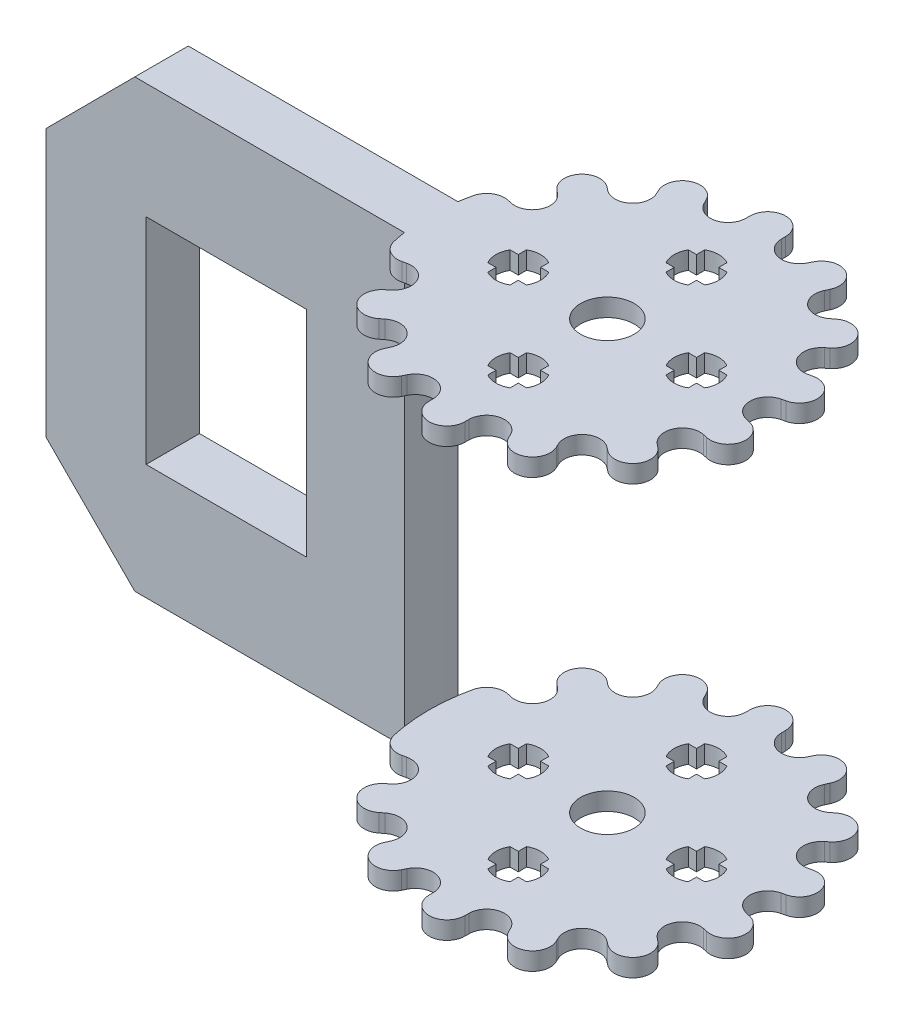
SolidWorks part; units mm, degrees
note: '?' marks a value the reader was unsure of. The reader was unsure of these and kept them because the rebuilt part matched: shared geometry of "Croquis1<3>".
material "PLA"
ref_plane "Alzado" through (0, 0, 0) normal (0, 0, 1) x (1, 0, 0)
ref_plane "Planta" through (0, 0, 0) normal (0, 1, 0) x (1, 0, 0)
ref_plane "Vista lateral" through (0, 0, 0) normal (1, 0, 0) x (0, 0, -1)
sketch "Croquis1" plane through (0, 0, 0) normal (0, 1, 0) x (1, 0, 0)
  line L4 (-60, -20) -> (-60, -14)
  line L5 (-60, -20) -> (0, -20)
  line L6 (0, 0) -> (-60, 0) construction
  line L7 (-60, 0) -> (-60, 3) construction
  line L8 (-60, 3) -> (-60, -14)
  line L9 (-60, 3) -> (-19.7737, 3)
  circle A0 centre (0, 0) radius 20 construction
  arc A1 (-14.2829, -14) -> (0, -20) centre (0, 0) ccw
  arc A2 (-14.1107, -14.1735) -> (0, -20) centre (0, 0) cw
extrude "Saliente-Extruir1" add sketch "Croquis1" along normal blind 50
extrude "Saliente-Extruir2" add sketch "Croquis1<3>" along normal blind 2 contours A2 A1
sketch "Croquis1<3>" plane through (0, 0, 0) normal (0, 1, 0) x (1, 0, 0) same geometry as "Croquis1"
ref_plane "Plano1" through (0, 25, 0) normal (0, 1, 0) x (1, 0, 0)
mirror "Simetría1" about plane through (0, 25, 0) normal (0, 1, 0) of "Saliente-Extruir2"
sketch "Croquis2" plane through (0, 50, 0) normal (0, 1, 0) x (1, 0, 0)
  line L0 (2, 18) -> (2.0054, 17.5487)
  line L1 (0, 20) -> (0, 16) construction
  line L2 (9.6118, 15.3497) -> (9.4209, 14.9407)
  line L3 (15.3199, 9.6592) -> (14.9705, 9.3736)
  line L4 (17.9937, 2.0555) -> (17.555, 1.9499)
  line L5 (17.1037, -5.9552) -> (16.6625, -5.8601)
  line L6 (12.826, -12.7865) -> (12.4698, -12.5093)
  line L7 (6.008, -17.0852) -> (5.8073, -16.6809)
  line L8 (-2, -18) -> (-2.0054, -17.5487)
  line L9 (-9.6118, -15.3497) -> (-9.4209, -14.9407)
  line L10 (-15.3199, -9.6592) -> (-14.9705, -9.3736)
  line L11 (-17.9937, -2.0555) -> (-17.555, -1.9499)
  line L12 (-17.1037, 5.9552) -> (-16.6625, 5.8601)
  line L13 (-12.826, 12.7865) -> (-12.4698, 12.5093)
  line L14 (-6.008, 17.0852) -> (-5.8073, 16.6809)
  line L15 (-2, 18) -> (-2.0054, 17.5487)
  line L16 (6.008, 17.0852) -> (5.8073, 16.6809)
  line L17 (12.826, 12.7865) -> (12.4698, 12.5093)
  line L18 (17.1037, 5.9552) -> (16.6625, 5.8601)
  line L19 (17.9937, -2.0555) -> (17.555, -1.9499)
  line L20 (15.3199, -9.6592) -> (14.9705, -9.3736)
  line L21 (9.6118, -15.3497) -> (9.4209, -14.9407)
  line L22 (2, -18) -> (2.0054, -17.5487)
  line L23 (-6.008, -17.0852) -> (-5.8073, -16.6809)
  line L24 (-12.826, -12.7865) -> (-12.4698, -12.5093)
  line L25 (-17.1037, -5.9552) -> (-16.6625, -5.8601)
  line L26 (-17.9937, 2.0555) -> (-17.555, 1.9499)
  line L27 (-15.3199, 9.6592) -> (-14.9705, 9.3736)
  line L28 (-9.6118, 15.3497) -> (-9.4209, 14.9407)
  circle A0 centre (0, 0) radius 20 construction
  circle A1 centre (0, 0) radius 16 construction
  circle A2 centre (0, 18) radius 2 construction
  circle A3 centre (4.0054, 17.5487) radius 2 construction
  circle A4 centre (7.8099, 16.2174) radius 2 construction
  circle A5 centre (11.2228, 14.073) radius 2 construction
  circle A6 centre (14.073, 11.2228) radius 2 construction
  circle A7 centre (16.2174, 7.8099) radius 2 construction
  circle A8 centre (17.5487, 4.0054) radius 2 construction
  circle A9 centre (18, 0) radius 2 construction
  circle A10 centre (17.5487, -4.0054) radius 2 construction
  circle A11 centre (16.2174, -7.8099) radius 2 construction
  circle A12 centre (14.073, -11.2228) radius 2 construction
  circle A13 centre (11.2228, -14.073) radius 2 construction
  circle A14 centre (7.8099, -16.2174) radius 2 construction
  circle A15 centre (4.0054, -17.5487) radius 2 construction
  circle A16 centre (0, -18) radius 2 construction
  circle A17 centre (-4.0054, -17.5487) radius 2 construction
  circle A18 centre (-7.8099, -16.2174) radius 2 construction
  circle A19 centre (-11.2228, -14.073) radius 2 construction
  circle A20 centre (-14.073, -11.2228) radius 2 construction
  circle A21 centre (-16.2174, -7.8099) radius 2 construction
  circle A22 centre (-17.5487, -4.0054) radius 2 construction
  circle A23 centre (-18, 0) radius 2 construction
  circle A24 centre (-17.5487, 4.0054) radius 2 construction
  circle A25 centre (-16.2174, 7.8099) radius 2 construction
  circle A26 centre (-14.073, 11.2228) radius 2 construction
  circle A27 centre (-11.2228, 14.073) radius 2 construction
  circle A28 centre (-7.8099, 16.2174) radius 2 construction
  circle A29 centre (-4.0054, 17.5487) radius 2 construction
  arc A30 (-2, 18) -> (2, 18) centre (0, 18) cw
  arc A31 (2.0054, 17.5487) -> (4.0054, 15.5487) centre (4.0054, 17.5487) ccw
  arc A32 (6.008, 17.0852) -> (9.6118, 15.3497) centre (7.8099, 16.2174) cw
  arc A33 (9.4209, 14.9407) -> (10.355, 12.271) centre (11.2228, 14.073) ccw
  arc A34 (12.826, 12.7865) -> (15.3199, 9.6592) centre (14.073, 11.2228) cw
  arc A35 (14.9705, 9.3736) -> (14.6538, 6.5629) centre (16.2174, 7.8099) ccw
  arc A36 (17.1037, 5.9552) -> (17.9937, 2.0555) centre (17.5487, 4.0054) cw
  arc A37 (17.555, 1.9499) -> (16.0501, -0.445) centre (18, 0) ccw
  arc A38 (17.9937, -2.0555) -> (17.1037, -5.9552) centre (17.5487, -4.0054) cw
  arc A39 (16.6625, -5.8601) -> (14.2676, -7.3649) centre (16.2174, -7.8099) ccw
  arc A40 (15.3199, -9.6592) -> (12.826, -12.7865) centre (14.073, -11.2228) cw
  arc A41 (12.4698, -12.5093) -> (9.6592, -12.826) centre (11.2228, -14.073) ccw
  arc A42 (9.6118, -15.3497) -> (6.008, -17.0852) centre (7.8099, -16.2174) cw
  arc A43 (5.8073, -16.6809) -> (3.1376, -15.7468) centre (4.0054, -17.5487) ccw
  arc A44 (2, -18) -> (-2, -18) centre (0, -18) cw
  arc A45 (-2.0054, -17.5487) -> (-4.0054, -15.5487) centre (-4.0054, -17.5487) ccw
  arc A46 (-6.008, -17.0852) -> (-9.6118, -15.3497) centre (-7.8099, -16.2174) cw
  arc A47 (-9.4209, -14.9407) -> (-10.355, -12.271) centre (-11.2228, -14.073) ccw
  arc A48 (-12.826, -12.7865) -> (-15.3199, -9.6592) centre (-14.073, -11.2228) cw
  arc A49 (-14.9705, -9.3736) -> (-14.6538, -6.5629) centre (-16.2174, -7.8099) ccw
  arc A50 (-17.1037, -5.9552) -> (-17.9937, -2.0555) centre (-17.5487, -4.0054) cw
  arc A51 (-17.555, -1.9499) -> (-16.0501, 0.445) centre (-18, 0) ccw
  arc A52 (-17.9937, 2.0555) -> (-17.1037, 5.9552) centre (-17.5487, 4.0054) cw
  arc A53 (-16.6625, 5.8601) -> (-14.2676, 7.3649) centre (-16.2174, 7.8099) ccw
  arc A54 (-15.3199, 9.6592) -> (-12.826, 12.7865) centre (-14.073, 11.2228) cw
  arc A55 (-12.4698, 12.5093) -> (-9.6592, 12.826) centre (-11.2228, 14.073) ccw
  arc A56 (-9.6118, 15.3497) -> (-6.008, 17.0852) centre (-7.8099, 16.2174) cw
  arc A57 (-5.8073, 16.6809) -> (-3.1376, 15.7468) centre (-4.0054, 17.5487) ccw
  arc A58 (-2.0054, 17.5487) -> (-3.1376, 15.7468) centre (-4.0054, 17.5487) cw
  arc A59 (5.8073, 16.6809) -> (4.0054, 15.5487) centre (4.0054, 17.5487) cw
  arc A60 (12.4698, 12.5093) -> (10.355, 12.271) centre (11.2228, 14.073) cw
  arc A61 (16.6625, 5.8601) -> (14.6538, 6.5629) centre (16.2174, 7.8099) cw
  arc A62 (17.555, -1.9499) -> (16.0501, -0.445) centre (18, 0) cw
  arc A63 (14.9705, -9.3736) -> (14.2676, -7.3649) centre (16.2174, -7.8099) cw
  arc A64 (9.4209, -14.9407) -> (9.6592, -12.826) centre (11.2228, -14.073) cw
  arc A65 (2.0054, -17.5487) -> (3.1376, -15.7468) centre (4.0054, -17.5487) cw
  arc A66 (-5.8073, -16.6809) -> (-4.0054, -15.5487) centre (-4.0054, -17.5487) cw
  arc A67 (-12.4698, -12.5093) -> (-10.355, -12.271) centre (-11.2228, -14.073) cw
  arc A68 (-16.6625, -5.8601) -> (-14.6538, -6.5629) centre (-16.2174, -7.8099) cw
  arc A69 (-17.555, 1.9499) -> (-16.0501, 0.445) centre (-18, 0) cw
  arc A70 (-14.9705, 9.3736) -> (-14.2676, 7.3649) centre (-16.2174, 7.8099) cw
  arc A71 (-9.4209, 14.9407) -> (-9.6592, 12.826) centre (-11.2228, 14.073) cw
  point P65 (0, 0)
  point P150 (0, 0)
  point P206 (0, 0)
  dimension "D1" = 28
  dimension "D2" = 14
  dimension "D3" = 14
extrude "Cortar-Extruir2" cut sketch "Croquis2" against normal blind 2 contours A62 L19 A38 A2 A36 L4 A37 | A61 L18 A36 A2 A34 L3 A35 | A70 L27 A54 A2 A52 L12 A53 | A71 L28 A56 A2 A54 L13 A55 | A58 L15 A30 A2 A56 L14 A57 | A59 L16 A32 A2 A30 L0 A31 | A60 L17 A34 A2 A32 L2 A33 | A63 L20 A40 A2 A38 L5 A39 | A64 L21 A42 A2 A40 L6 A41 | A65 L22 A44 A2 A42 L7 A43
mirror "Simetría2" about plane through (0, 25, 0) normal (0, 1, 0) of "Cortar-Extruir2"
sketch "Croquis3" plane through (0, 50, 0) normal (0, 1, 0) x (1, 0, 0)
  circle A0 centre (0, 0) radius 3
  point P4 (0, 0)
extrude "Cortar-Extruir3" cut sketch "Croquis3" against normal up to next
mirror "Simetría3" about plane through (0, 25, 0) normal (0, 1, 0) of "Cortar-Extruir3"
ref_plane "Plano2" through (0, 25, 0) normal (0, -1, 0) x (-1, 0, 0)
sketch "Croquis5" plane through (0, 25, 0) normal (0, -1, 0) x (-1, 0, 0)
  line L1 (-22.6575, 23.4045) -> (62.2625, 23.4045)
  line L2 (-22.6575, 23.4045) -> (-22.6575, -22.6962)
  line L3 (-22.6575, -22.6962) -> (62.2625, -22.6962)
  line L4 (62.2625, 23.4045) -> (62.2625, -22.6962)
  line L5 (-22.6575, 23.4045) -> (62.2625, -22.6962) construction
  line L6 (-22.6575, -22.6962) -> (62.2625, 23.4045) construction
  point P0 (19.8025, 0.3542)
ref_axis "Eje1" through (0, 0, 0) along (0, 1, 0)?
sketch "Croquis8" plane through (0, 50, 0) normal (0, 1, 0) x (1, 0, 0)
  line L0 (0, 0) -> (-60, 0) construction
  line L1 (-60, 0) -> (-60, -3) construction
  line L2 (-60, 3) -> (-60, -14) construction
  line L3 (-60, -3) -> (-19.7737, -3)
  line L4 (-60, -3) -> (-60, -20)
  line L5 (-60, -20) -> (0, -20)
  arc A0 (0, -20) -> (-14.1107, -14.1735) centre (0, 0) ccw construction
  arc A1 (-19.7737, -3) -> (0, -20) centre (0, 0) ccw
extrude "Cortar-Extruir6" cut sketch "Croquis8" against normal through all
sketch "Croquis9" plane through (0, 50, 0) normal (0, 1, 0) x (1, 0, 0)
  line L0 (-2.0054, -17.5487) -> (-2, -18)
  line L1 (-5.8073, -16.6809) -> (-6.008, -17.0852)
  line L2 (-9.4209, -14.9407) -> (-9.6118, -15.3497)
  line L3 (-12.4698, -12.5093) -> (-12.826, -12.7865)
  line L4 (-15.3199, -9.6592) -> (-14.9705, -9.3736)
  line L5 (-16.6625, -5.8601) -> (-17.1037, -5.9552)
  arc A0 (-19.4986, -4.4504) -> (-17.1037, -5.9552) centre (-17.5487, -4.0054) ccw
  arc A1 (-17.9937, -2.0555) -> (-17.1037, -5.9552) centre (-17.5487, -4.0054) ccw construction
  arc A2 (-16.6625, -5.8601) -> (-14.9705, -9.3736) centre (-16.2174, -7.8099) cw
  arc A3 (-15.3199, -9.6592) -> (-12.826, -12.7865) centre (-14.073, -11.2228) ccw
  arc A4 (-12.4698, -12.5093) -> (-9.4209, -14.9407) centre (-11.2228, -14.073) cw
  arc A5 (-9.6118, -15.3497) -> (-6.008, -17.0852) centre (-7.8099, -16.2174) ccw
  arc A6 (-5.8073, -16.6809) -> (-2.0054, -17.5487) centre (-4.0054, -17.5487) cw
  arc A7 (-2, -18) -> (0, -20) centre (0, -18) ccw
  circle A8 centre (0, 0) radius 20
  arc M2 (-19.7737, -3) -> (0, -20) centre (0, 0) ccw
extrude "Cortar-Extruir7" cut sketch "Croquis9" against normal through all contours A3 L4 A2 L5 A0 M2 | A5 L2 A4 L3 A3 M2 | A7 L0 A6 L1 A5 M2
sketch "Croquis10" plane through (0, 0, 3) normal (0, 0, 1) x (1, 0, 0)
  line L0 (-19.7737, 25) -> (-59.7459, 25) construction
  line L1 (-19.7737, 2) -> (-19.7737, 48) construction
  line L2 (-22, 25) -> (22, 25) construction
  line L3 (-39.7598, 25) -> (-39.7598, 37.0385) construction
  line L4 (-48.7712, 37.0385) -> (-30.7484, 37.0385)
  line L5 (-30.7484, 37.0385) -> (-30.7484, 12.9615)
  line L6 (-48.7712, 37.0385) -> (-48.7712, 12.9615)
  line L7 (-48.7712, 12.9615) -> (-30.7484, 12.9615)
  line L8 (-60, 50) -> (-60, 40)
  line L9 (-60, 0) -> (-60, 50) construction
  line L10 (-60, 50) -> (-50.0325, 50)
  line L11 (-19.7737, 50) -> (-60, 50) construction
  line L12 (-50.0325, 50) -> (-60, 40)
  line L13 (-60, 0) -> (-60, 10)
  line L14 (-50.0325, 0) -> (-60, 10)
  point P13 (-30.7484, 25)
  point P14 (-48.7712, 25)
  line M8 (-19.7737, 50) -> (-60, 50)
  line M9 (-60, 50) -> (-60, 0)
  line M10 (-60, 0) -> (-19.7737, 0)
extrude "Cortar-Extruir8" cut sketch "Croquis10" against normal blind 10 contours L12 M8 M9 | L6 L7 L5 L4 | L14 M10 M9
sketch "Croquis15" plane through (0, 50, 0) normal (0, 1, 0) x (1, 0, 0)
  line L0 (0, 10) -> (2.5, 10) construction
  line L1 (1.25, 10) -> (1.25, 12.1651) construction
  line L2 (0, 10) -> (0, 12.5) construction
  line L3 (0, 12.5) -> (0, 11.25) construction
  line L4 (0, 11.25) -> (2.1651, 11.25) construction
  line L5 (1.25, 12.1651) -> (1.25, 11.25)
  line L6 (1.25, 11.25) -> (2.1651, 11.25)
  line L7 (2.1651, 8.75) -> (1.25, 8.75)
  line L8 (1.25, 8.75) -> (1.25, 7.8349)
  line L9 (-1.25, 7.8349) -> (-1.25, 8.75)
  line L10 (-1.25, 8.75) -> (-2.1651, 8.75)
  line L11 (-2.1651, 11.25) -> (-1.25, 11.25)
  line L12 (-1.25, 11.25) -> (-1.25, 12.1651)
  line L13 (11.25, -1.25) -> (11.25, -2.1651)
  line L14 (12.1651, -1.25) -> (11.25, -1.25)
  line L15 (8.75, -2.1651) -> (8.75, -1.25)
  line L16 (8.75, -1.25) -> (7.8349, -1.25)
  line L17 (7.8349, 1.25) -> (8.75, 1.25)
  line L18 (8.75, 1.25) -> (8.75, 2.1651)
  line L19 (11.25, 2.1651) -> (11.25, 1.25)
  line L20 (11.25, 1.25) -> (12.1651, 1.25)
  line L21 (-1.25, -11.25) -> (-2.1651, -11.25)
  line L22 (-1.25, -12.1651) -> (-1.25, -11.25)
  line L23 (-2.1651, -8.75) -> (-1.25, -8.75)
  line L24 (-1.25, -8.75) -> (-1.25, -7.8349)
  line L25 (1.25, -7.8349) -> (1.25, -8.75)
  line L26 (1.25, -8.75) -> (2.1651, -8.75)
  line L27 (2.1651, -11.25) -> (1.25, -11.25)
  line L28 (1.25, -11.25) -> (1.25, -12.1651)
  line L29 (-11.25, 1.25) -> (-11.25, 2.1651)
  line L30 (-12.1651, 1.25) -> (-11.25, 1.25)
  line L31 (-8.75, 2.1651) -> (-8.75, 1.25)
  line L32 (-8.75, 1.25) -> (-7.8349, 1.25)
  line L33 (-7.8349, -1.25) -> (-8.75, -1.25)
  line L34 (-8.75, -1.25) -> (-8.75, -2.1651)
  line L35 (-11.25, -2.1651) -> (-11.25, -1.25)
  line L36 (-11.25, -1.25) -> (-12.1651, -1.25)
  circle A0 centre (0, 0) radius 10 construction
  circle A1 centre (0, 10) radius 2.5 construction
  arc A2 (0, 12.5) -> (1.25, 12.1651) centre (0, 10) cw
  arc A3 (2.1651, 11.25) -> (2.5, 10) centre (0, 10) cw
  arc A4 (2.5, 10) -> (2.1651, 8.75) centre (0, 10) cw
  arc A5 (1.25, 7.8349) -> (0, 7.5) centre (0, 10) cw
  arc A6 (0, 7.5) -> (-1.25, 7.8349) centre (0, 10) cw
  arc A7 (-2.1651, 8.75) -> (-2.5, 10) centre (0, 10) cw
  arc A8 (-2.5, 10) -> (-2.1651, 11.25) centre (0, 10) cw
  arc A9 (-1.25, 12.1651) -> (0, 12.5) centre (0, 10) cw
  arc A10 (12.1651, 1.25) -> (12.5, 0) centre (10, 0) cw
  arc A11 (12.5, 0) -> (12.1651, -1.25) centre (10, 0) cw
  arc A12 (11.25, -2.1651) -> (10, -2.5) centre (10, 0) cw
  arc A13 (10, -2.5) -> (8.75, -2.1651) centre (10, 0) cw
  arc A14 (7.8349, -1.25) -> (7.5, 0) centre (10, 0) cw
  arc A15 (7.5, 0) -> (7.8349, 1.25) centre (10, 0) cw
  arc A16 (8.75, 2.1651) -> (10, 2.5) centre (10, 0) cw
  arc A17 (10, 2.5) -> (11.25, 2.1651) centre (10, 0) cw
  arc A18 (1.25, -12.1651) -> (0, -12.5) centre (0, -10) cw
  arc A19 (0, -12.5) -> (-1.25, -12.1651) centre (0, -10) cw
  arc A20 (-2.1651, -11.25) -> (-2.5, -10) centre (0, -10) cw
  arc A21 (-2.5, -10) -> (-2.1651, -8.75) centre (0, -10) cw
  arc A22 (-1.25, -7.8349) -> (0, -7.5) centre (0, -10) cw
  arc A23 (0, -7.5) -> (1.25, -7.8349) centre (0, -10) cw
  arc A24 (2.1651, -8.75) -> (2.5, -10) centre (0, -10) cw
  arc A25 (2.5, -10) -> (2.1651, -11.25) centre (0, -10) cw
  arc A26 (-12.1651, -1.25) -> (-12.5, 0) centre (-10, 0) cw
  arc A27 (-12.5, 0) -> (-12.1651, 1.25) centre (-10, 0) cw
  arc A28 (-11.25, 2.1651) -> (-10, 2.5) centre (-10, 0) cw
  arc A29 (-10, 2.5) -> (-8.75, 2.1651) centre (-10, 0) cw
  arc A30 (-7.8349, 1.25) -> (-7.5, 0) centre (-10, 0) cw
  arc A31 (-7.5, 0) -> (-7.8349, -1.25) centre (-10, 0) cw
  arc A32 (-8.75, -2.1651) -> (-10, -2.5) centre (-10, 0) cw
  arc A33 (-10, -2.5) -> (-11.25, -2.1651) centre (-10, 0) cw
  point P32 (0, 10)
  point P91 (0, 0)
  dimension "D1" = 4
  dimension "D2" = 4
extrude "Cortar-Extruir9" cut sketch "Croquis15" against normal through all contours A9 L12 L11 A8 A7 L10 L9 A6 A5 L8 L7 A4 A3 L6 L5 A2 | A33 A32 L34 L33 A31 A30 L32 L31 A29 A28 L29 L30 A27 A26 L36 L35 | A17 A16 L18 L17 A15 A14 L16 L15 A13 A12 L13 L14 A11 A10 L20 L19 | A25 A24 L26 L25 A23 A22 L24 L23 A21 A20 L21 L22 A19 A18 L28 L27
ref_plane "Plano3" through (0, 25, 0) normal (0, 1, 0) x (1, 0, 0)
sketch "Croquis16" plane through (0, 25, 0) normal (0, 1, 0) x (1, 0, 0)
  line L1 (-65.8044, 24.0011) -> (26.0055, 24.0011)
  line L2 (-65.8044, 24.0011) -> (-65.8044, -24.2807)
  line L3 (-65.8044, -24.2807) -> (26.0055, -24.2807)
  line L4 (26.0055, 24.0011) -> (26.0055, -24.2807)
